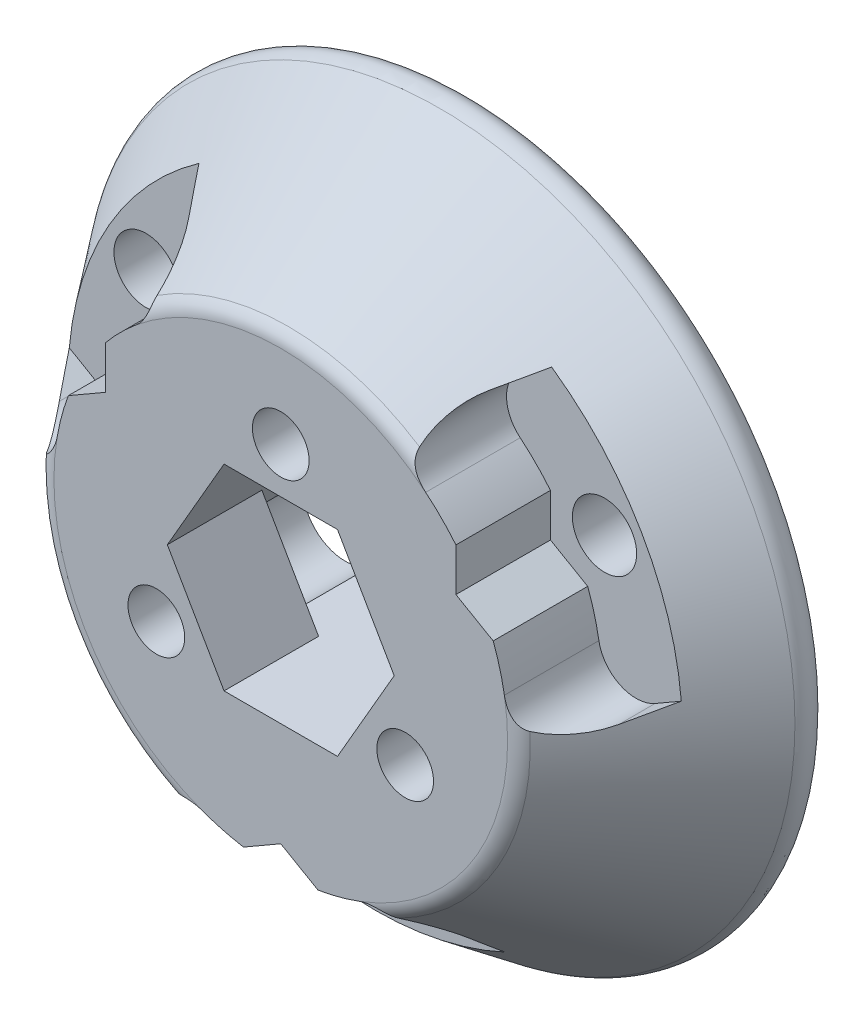
SolidWorks part; units mm, degrees
ref_plane "前视基准面" through (0, 0, 0) normal (0, 0, 1) x (1, 0, 0)
ref_plane "上视基准面" through (0, 0, 0) normal (0, 1, 0) x (1, 0, 0)
ref_plane "右视基准面" through (0, 0, 0) normal (1, 0, 0) x (0, 0, -1)
sketch "草图1" plane through (0, 0, 0) normal (0, 0, 1) x (1, 0, 0)
  circle A0 centre (0, 0) radius 20
  dimension "D1" = 40
ref_plane "基准面1" through (0, 0, 10) normal (0, 0, 1) x (1, 0, 0)
sketch "草图2" plane through (0, 0, 10) normal (0, 0, 1) x (1, 0, 0)
  circle A0 centre (0, 0) radius 12.5
  dimension "D1" = 25
loft "放样1" add profiles "草图1", "草图2" connector at (19.5183, 4.3629, 0) connector at (12.4329, 1.2936, 10)
fillet "圆角1" radius 1 2 edges at (12.5, 0, 10) (20, 0, 0)
sketch "草图3" plane through (0, 0, 0) normal (0, 0, -1) x (-1, 0, 0)
  line L0 (0, 0) -> (0, -14) construction
  line L1 (0, 0) -> (0, 7.6) construction
  line L2 (-12.1244, 7) -> (0, 0) construction
  circle A0 centre (0, 0) radius 14 construction
  circle A1 centre (0, -14) radius 1.7
  circle A4 centre (0, 0) radius 7.6 construction
  circle A5 centre (0, 7.6) radius 1.5
  circle A8 centre (-12.1244, 7) radius 1.7
  circle A9 centre (12.1244, 7) radius 1.7
  circle A10 centre (6.5818, -3.8) radius 1.5
  circle A11 centre (-6.5818, -3.8) radius 1.5
  point P15 (0, 0)
  point P19 (0, 0)
  point P22 (0, 0)
  dimension "D1" = 28
  dimension "D2" = 3.4
  dimension "D4" = 15.2
  dimension "D5" = 3
  dimension "D7" = 3
  dimension "D6" = 120
  dimension "D3" = 3
extrude "切除-拉伸1" cut sketch "草图3" against normal through all
sketch "草图5" plane through (0, 0, 0) normal (0, 0, -1) x (-1, 0, 0)
  line L0 (0, 0) -> (0, 9.1) construction
  line L1 (-3, 5.1962) -> (-6, 0)
  line L2 (-6, 0) -> (-3, -5.1962)
  line L3 (-3, -5.1962) -> (3, -5.1962)
  line L4 (3, -5.1962) -> (6, 0)
  line L5 (6, 0) -> (3, 5.1962)
  line L6 (3, 5.1962) -> (-3, 5.1962)
  circle A0 centre (0, 0) radius 5.1962 construction
  circle A1 centre (0, 0) radius 6 construction
  circle A2 centre (0, 7.6) radius 1.5 construction
  point P10 (0, 5.1962)
  dimension "D1" = 12
extrude "切除-拉伸2" cut sketch "草图5" against normal through all
sketch "草图6" plane through (0, 0, 0) normal (0, 0, -1) x (-1, 0, 0)
  circle A0 centre (6.5818, -3.8) radius 2.25
  circle A2 centre (0, 7.6) radius 2.25
  circle A3 centre (-6.5818, -3.8) radius 2.25
  dimension "D1" = 4.5
  dimension "D2" = 4.5
  dimension "D3" = 4.5
extrude "切除-拉伸3" cut sketch "草图6" against normal blind 5
sketch "草图7" plane through (0, 0, 10) normal (0, 0, 1) x (1, 0, 0)
  line L0 (-6, 0) -> (-3, 5.1962) construction
  line L25 (3, 5.1962) -> (6, 0) construction
  line L26 (3, -5.1962) -> (-3, -5.1962) construction
  line L40 (-12.1244, 3.7) -> (-9.2665, 5.35)
  line L41 (-9.2665, 5.35) -> (-9.2665, 8.65)
  line L42 (-9.2665, 8.65) -> (-12.1244, 10.3)
  line L43 (-12.1244, 10.3) -> (-14.9822, 8.65)
  line L44 (-14.9822, 8.65) -> (-14.9822, 5.35)
  line L45 (-14.9822, 5.35) -> (-12.1244, 3.7)
  line L52 (14.9822, 5.35) -> (14.9822, 8.65)
  line L53 (14.9822, 8.65) -> (12.1244, 10.3)
  line L54 (12.1244, 10.3) -> (9.2665, 8.65)
  line L55 (9.2665, 8.65) -> (9.2665, 5.35)
  line L56 (9.2665, 5.35) -> (12.1244, 3.7)
  line L57 (12.1244, 3.7) -> (14.9822, 5.35)
  line L58 (0, -17.3) -> (2.8579, -15.65)
  line L59 (2.8579, -15.65) -> (2.8579, -12.35)
  line L60 (2.8579, -12.35) -> (0, -10.7)
  line L61 (0, -10.7) -> (-2.8579, -12.35)
  line L62 (-2.8579, -12.35) -> (-2.8579, -15.65)
  line L63 (-2.8579, -15.65) -> (0, -17.3)
  circle A4 centre (-12.1244, 7) radius 2.8579 construction
  arc A10 (-10.4652, 7.3702) -> (-11.6154, 5.378) centre (-12.1244, 7) ccw construction
  circle A11 centre (12.1244, 7) radius 2.8579 construction
  circle A12 centre (0, -14) radius 2.8579 construction
  arc A16 (11.6154, 5.378) -> (10.4652, 7.3702) centre (12.1244, 7) ccw construction
  arc A17 (-1.1502, -12.7482) -> (1.1502, -12.7482) centre (0, -14) ccw construction
  dimension "D1" = 3.3
  dimension "D2" = 3.3
  dimension "D3" = 3.3
extrude "切除-拉伸4" cut sketch "草图7" against normal blind 5
sketch "草图9" plane through (0, 0, 10) normal (0, 0, 1) x (1, 0, 0)
  line L0 (-12.1244, 3.7) -> (-9.2665, 5.35) construction
  line L1 (-9.2665, 5.35) -> (-9.2665, 7.6245) construction
  line L2 (-11.2362, 4.2128) -> (-9.2665, 5.35)
  line L3 (-9.2665, 5.35) -> (-9.2665, 7.6245)
  line L8 (-11.957, -1.0154) -> (-16.1872, 1.4269)
  line L9 (-5.0991, 10.8628) -> (-9.3293, 13.3051)
  line L10 (-12.2342, 3.7634) -> (-14.9822, 5.35) construction
  line L11 (-9.2665, 8.65) -> (-12.1244, 10.3) construction
  line L12 (-14.9822, 5.35) -> (-12.1244, 3.7) construction
  line L13 (-12.1244, 10.3) -> (-9.3764, 8.7134) construction
  line L14 (11.957, -1.0154) -> (16.1872, 1.4269)
  line L15 (5.0991, 10.8628) -> (9.3293, 13.3051)
  line L16 (9.2665, 7.6245) -> (9.2665, 5.35)
  line L17 (9.2665, 5.35) -> (11.2362, 4.2128)
  line L18 (-6.8579, -9.8473) -> (-6.8579, -14.732)
  line L19 (6.8579, -9.8473) -> (6.8579, -14.732)
  line L20 (1.9697, -11.8372) -> (0, -10.7)
  line L21 (0, -10.7) -> (-1.9697, -11.8372)
  arc A6 (-12.9405, 9.8288) -> (-14.9822, 6.2925) centre (0, 0) ccw construction
  arc A7 (-9.3293, 13.3051) -> (-16.1872, 1.4269) centre (0, 0) ccw
  arc A8 (-11.2362, 4.2128) -> (-1.9697, -11.8372) centre (0, 0) ccw construction
  arc A9 (9.2665, 7.6245) -> (-9.2665, 7.6245) centre (0, 0) ccw construction
  arc A10 (-11.2362, 4.2128) -> (-11.957, -1.0154) centre (0, 0) ccw
  arc A11 (-5.0991, 10.8628) -> (-9.2665, 7.6245) centre (0, 0) ccw
  arc A19 (16.1872, 1.4269) -> (9.3293, 13.3051) centre (0, 0) ccw
  arc A20 (9.2665, 7.6245) -> (5.0991, 10.8628) centre (0, 0) ccw
  arc A21 (11.957, -1.0154) -> (11.2362, 4.2128) centre (0, 0) ccw
  arc A22 (-6.8579, -14.732) -> (6.8579, -14.732) centre (0, 0) ccw
  arc A23 (1.9697, -11.8372) -> (6.8579, -9.8473) centre (0, 0) ccw
  arc A24 (-6.8579, -9.8473) -> (-1.9697, -11.8372) centre (0, 0) ccw
  point P35 (0, 0)
  point P37 (0, 0)
  dimension "D1" = 4
  dimension "D2" = 4
  dimension "D3" = 3
extrude "切除-拉伸5" cut sketch "草图9" against normal up to surface (5 mm away) up to face at (-12.2569, 7.0765, 5)
fillet "圆角2" radius 2 6 edges at (-6.8579, -9.8473, 7.5) (6.8579, -9.8473, 7.5) (-11.957, -1.0154, 7.5) (-5.0991, 10.8628, 7.5) (5.0991, 10.8628, 7.5) (11.957, -1.0154, 7.5)
sketch "草图10" plane through (0, 0, 0) normal (0, 0, -1) x (-1, 0, 0)
  line L0 (-3, 5.1962) -> (-2.0913, 6.77)
  line L1 (-2.0913, 6.77) -> (2.0913, 6.77)
  line L2 (2.0913, 6.77) -> (3, 5.1962)
  line L3 (6, 0) -> (6.9087, -1.5739)
  line L4 (6.9087, -1.5739) -> (4.8174, -5.1962)
  line L5 (4.8174, -5.1962) -> (3, -5.1962)
  line L6 (-6, 0) -> (-6.9087, -1.5739)
  line L7 (-6.9087, -1.5739) -> (-4.8174, -5.1962)
  line L8 (-4.8174, -5.1962) -> (-3, -5.1962)
  line L10 (-3, 5.1962) -> (-6, 0) construction
  line L11 (6, 0) -> (3, 5.1962) construction
  line L12 (-3, -5.1962) -> (3, -5.1962) construction
  line L13 (-3, 5.1962) -> (-6, 0)
  line L14 (-3, -5.1962) -> (3, -5.1962)
  line L15 (6, 0) -> (3, 5.1962)
  circle A0 centre (0, 7.6) radius 2.25 construction
  circle A1 centre (0, 7.6) radius 2.25 construction
  circle A2 centre (6.5818, -3.8) radius 2.25 construction
  circle A3 centre (-6.5818, -3.8) radius 2.25 construction
  arc A4 (-6.9087, -1.5739) -> (-4.8174, -5.1962) centre (-6.5818, -3.8) ccw
  point P23 (-4.7847, -5.1962)
  point P24 (-4.8174, -5.1962)
  circle M12 centre (6.5818, -3.8) radius 2.25
  circle M13 centre (-6.5818, -3.8) radius 2.25
  circle M14 centre (0, 7.6) radius 2.25
  line M16 (-3, 5.1962) -> (3, 5.1962)
  line M18 (6, 0) -> (3, -5.1962)
  line M20 (-3, -5.1962) -> (-6, 0)
extrude "切除-拉伸6" cut sketch "草图10" against normal up to surface (5 mm away) contours L2 L0 M14 M16 | L8 L6 M13 M20 | L5 L3 M12 M18 region at (2.4919, 5.9521, 0) region at (4.5563, -2.6306, 0) region at (-6.398, -0.8194, 0) up to face at (-2.25, 7.6, 5)
